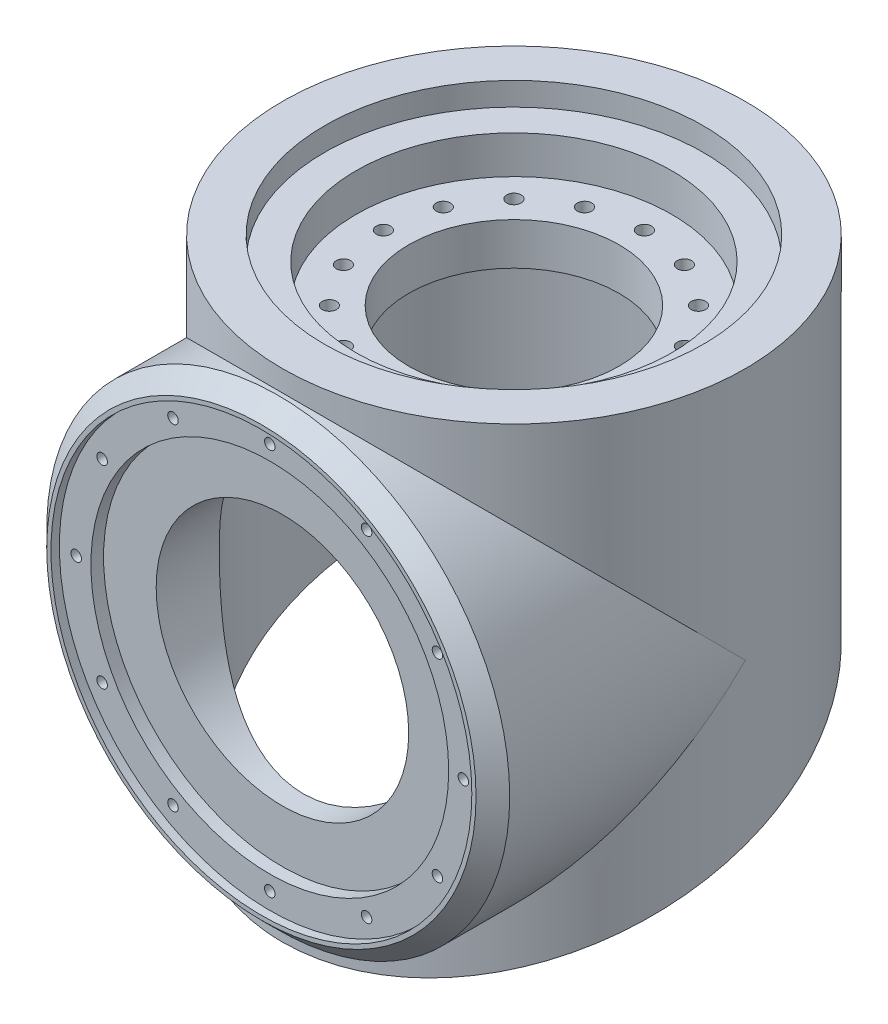
SolidWorks part; units mm, degrees
ref_plane "前视基准面" through (0, 0, 0) normal (0, 0, 1) x (1, 0, 0)
ref_plane "上视基准面" through (0, 0, 0) normal (0, 1, 0) x (1, 0, 0)
ref_plane "右视基准面" through (0, 0, 0) normal (1, 0, 0) x (0, 0, -1)
sketch "草图1" plane through (0, 0, 0) normal (0, 0, 1) x (1, 0, 0)
  circle A0 centre (0, 0) radius 55
  dimension "D1" = 110
extrude "凸台-拉伸1" add sketch "草图1" along normal blind 60
sketch "草图2" plane through (0, 0, 0) normal (0, 1, 0) x (1, 0, 0)
  circle A0 centre (0, 0) radius 55
extrude "凸台-拉伸2" add sketch "草图2" along normal blind 60 and the other way blind 58
sketch "草图3" plane through (0, -58, 0) normal (0, -1, 0) x (1, 0, 0)
  circle A0 centre (0, 0) radius 25
  dimension "D1" = 50
extrude "切除-拉伸1" cut sketch "草图3" against normal through all
sketch "草图4" plane through (0, 60, 0) normal (0, 1, 0) x (1, 0, 0)
  circle A0 centre (0, 0) radius 45
  dimension "D1" = 90
extrude "切除-拉伸2" cut sketch "草图4" against normal blind 5.5 contours A0
sketch "草图5" plane through (0, 54.5, 0) normal (0, 1, 0) x (1, 0, 0)
  circle A0 centre (0, 0) radius 37.5
  dimension "D1" = 75
extrude "切除-拉伸3" cut sketch "草图5" against normal blind 9
sketch "草图8" plane through (0, -58, 0) normal (0, -1, 0) x (1, 0, 0)
  circle A0 centre (0, 0) radius 50
  dimension "D1" = 100
extrude "切除-拉伸4" cut sketch "草图8" against normal offset from surface (93.5 mm away) 10 up to face at (0, 45.5, 37.5)
hole_wizard "打孔尺寸(%根据)内六角圆柱头螺钉的类型1" positions "草图10" profile "草图9" counterbore size "M3" standard "GB" end condition through all
sketch "草图10" plane through (0, 35.5, 0) normal (0, -1, 0) x (-1, 0, 0)
  line L0 (0, 0) -> (0, -41.8096) construction
  circle A0 centre (0, 0) radius 31 construction
  point P0 (0, -31)
  dimension "D1" = 62
sketch "草图9" plane through (0, 35.5, 31) normal (1, 0, 0) x (0, 0, -1)
  line L0 (0, 0) -> (0, 24.5)
  line L1 (0, 24.5) -> (1.7, 24.5)
  line L3 (1.7, 24.5) -> (1.7, 3.4)
  line L4 (1.7, 3.4) -> (3, 3.4)
  line L5 (3, 3.4) -> (3, 0)
  line L7 (3, 0) -> (0, 0)
  line L11 (0, -6.35) -> (0, 107.95) construction
  dimension "通孔孔直径" = 3.4
  dimension "通孔孔深度" = 24.5
  dimension "柱形沉头孔直径" = 6
  dimension "柱形沉头孔深度" = 3.4
ref_axis "基准轴2" through (0, 45.5, 0) along (0, -1, 0)
pattern_circular "阵列(圆周)2" count 16 over 360 about axis through (0, 45.5, 0) along (0, -1, 0) of "打孔尺寸(%根据)内六角圆柱头螺钉的类型1"
sketch "草图11" plane through (0, 0, 0) normal (1, 0, 0) x (0, 0, -1)
  line L0 (-55, -58) -> (55, -58)
  line L1 (55, -58) -> (55, -17.9633)
  line L2 (55, -58) -> (55, 60) construction
  line L3 (55, -17.9633) -> (-55, -58)
  dimension "D1" = 20
extrude "切除-拉伸5" cut sketch "草图11" against normal through all and the other way through all
ref_plane "基准面1" through (0, -58, 0) normal (0, 1, 0) x (1, 0, 0)
sketch "草图12" plane through (0, -58, 0) normal (0, 1, 0) x (1, 0, 0)
  line L0 (-68.853, 0) -> (68.4382, 0) construction
  circle A0 centre (0, 0) radius 52.5 construction
  circle A1 centre (52.5, 0) radius 1
  circle A2 centre (-52.5, 0) radius 1
  dimension "D1" = 105
  dimension "D2" = 2
extrude "切除-拉伸6" cut sketch "草图12" along normal blind 25
sketch "草图13" plane through (0, -58, 0) normal (0, 1, 0) x (1, 0, 0)
  line L0 (0, 0) -> (0, 66.6641) construction
  circle A0 centre (0, 0) radius 52.5 construction
  circle A1 centre (0, 52.5) radius 1
  dimension "D1" = 105
  dimension "D2" = 2
extrude "切除-拉伸7" cut sketch "草图13" along normal blind 48
sketch "草图14" plane through (0, -58, 0) normal (0, 1, 0) x (1, 0, 0)
  line L0 (0, 0) -> (0, -74.7111) construction
  circle A0 centre (0, 0) radius 52.5 construction
  circle A1 centre (0, -52.5) radius 1
  dimension "D1" = 105
  dimension "D2" = 2
extrude "切除-拉伸8" cut sketch "草图14" along normal blind 10
sketch "草图20" plane through (0, 0, 60) normal (0, 0, 1) x (1, 0, 0)
  circle A0 centre (0, 0) radius 50
  dimension "D1" = 100
extrude "切除-拉伸15" cut sketch "草图20" against normal blind 2 contours A0
sketch "草图18" plane through (0, 0, 60) normal (0, 0, 1) x (1, 0, 0)
  circle A0 centre (0, 0) radius 42.5
  dimension "D1" = 85
extrude "切除-拉伸12" cut sketch "草图18" against normal blind 5
hole_wizard "M3 螺纹孔2" positions "草图17" profile "草图16" tap size "M3" standard "GB"
sketch "草图17" plane through (0, 0, 60) normal (0, 0, 1) x (1, 0, 0)
  line L0 (0, 0) -> (0, 57.7786) construction
  line L1 (0, 45.5) -> (0, 35.5) construction
  circle A0 centre (0, 0) radius 46 construction
  point P0 (0, 46)
  dimension "D1" = 92
sketch "草图16" plane through (0, 46, 60) normal (1, 0, 0) x (0, -1, 0)
  line L0 (0, 0) -> (0, 8.2511)
  line L1 (0, 8.2511) -> (1.25, 7.5)
  line L2 (1.25, 7.5) -> (1.25, 0)
  line L5 (1.25, 0) -> (0, 0)
  line L10 (0, 8.2511) -> (-1.25, 7.5) construction
  line L11 (0, -6.35) -> (0, 107.95) construction
  dimension "螺纹孔钻头直径" = 2.5
  dimension "螺纹孔钻头深度" = 7.5
  dimension "导头角度" = 118
cosmetic thread "孔螺蚊线2" parameters "D1"=6, "D2"=3
ref_axis "基准轴3" through (0, 0, 55) along (0, 0, -1)
pattern_circular "阵列(圆周)3" count 12 over 360 about axis through (0, 0, 55) along (0, 0, -1) of "M3 螺纹孔2"
sketch "草图21" plane through (0, 0, 55) normal (0, 0, 1) x (1, 0, 0)
  circle A0 centre (0, 0) radius 30
  dimension "D1" = 60
extrude "切除-拉伸16" cut sketch "草图21" against normal blind 20
chamfer "倒角2" distance 4 angle 45 1 edges at (55, 0, 60)
